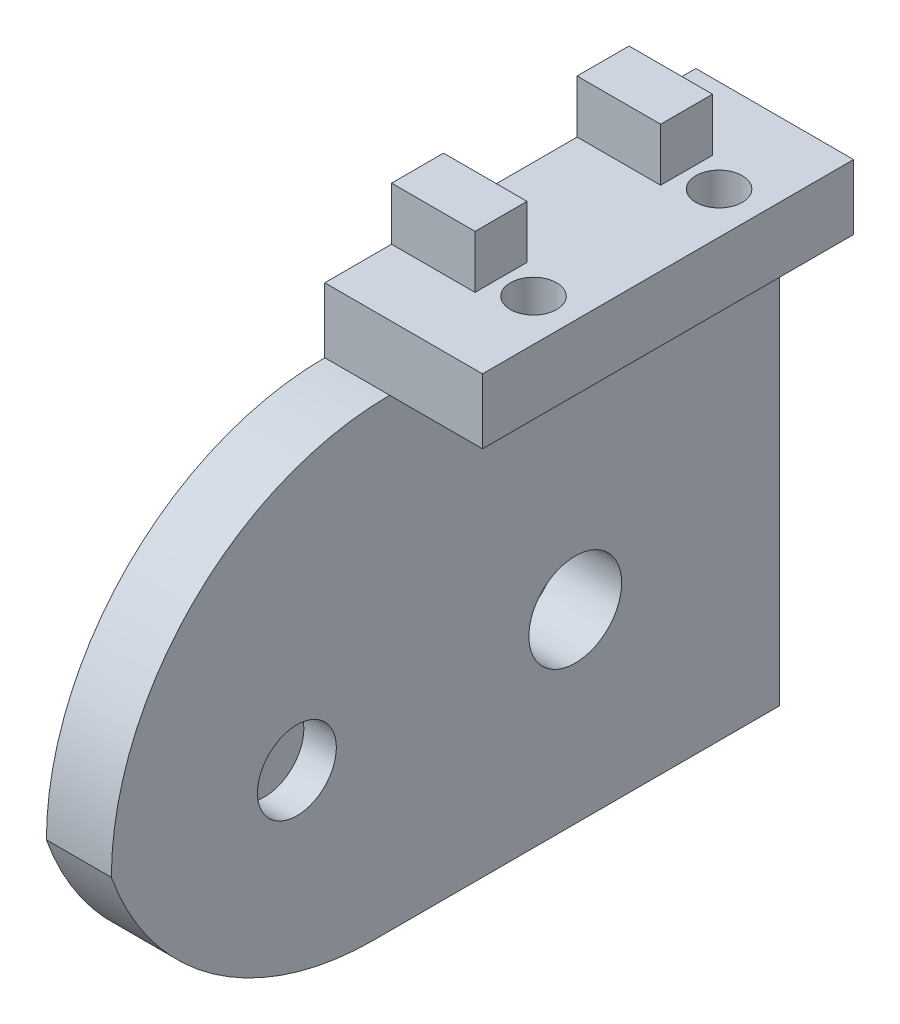
SolidWorks part; units mm, degrees
ref_plane "Alzado" through (0, 0, 0) normal (0, 0, 1) x (1, 0, 0)
ref_plane "Planta" through (0, 0, 0) normal (0, 1, 0) x (1, 0, 0)
ref_plane "Vista lateral" through (0, 0, 0) normal (1, 0, 0) x (0, 0, -1)
sketch "Croquis1" plane through (0, 0, 0) normal (0, 1, 0) x (1, 0, 0)
  line L1 (20, 20) -> (-20, 20)
  line L2 (20, 20) -> (20, -20)
  line L3 (20, -20) -> (-20, -20)
  line L4 (-20, 20) -> (-20, -20)
  line L5 (20, 20) -> (-20, -20) construction
  line L6 (20, -20) -> (-20, 20) construction
  point P0 (0, 0)
  dimension "D1" = 40
  dimension "D2" = 40
extrude "Saliente-Extruir1" add sketch "Croquis1" along normal blind 7
sketch "Croquis3" plane through (-20, 0, 0) normal (-1, 0, 0) x (0, 0, 1)
  line L0 (-20, 7) -> (20, 7) construction
  line L5 (-12.8, 12.7) -> (-7.2, 7) construction
  line L6 (7.2, 7) -> (12.8, 7)
  line L7 (7.2, 7) -> (7.2, 12.7)
  line L8 (7.2, 12.7) -> (12.8, 12.7)
  line L9 (12.8, 7) -> (12.8, 12.7)
  line L12 (-7.2, 7) -> (-12.8, 7)
  line L13 (-7.2, 7) -> (-7.2, 12.7)
  line L14 (-7.2, 12.7) -> (-12.8, 12.7)
  line L15 (-12.8, 7) -> (-12.8, 12.7)
  line L16 (-7.2, 12.7) -> (-12.8, 7) construction
  line L17 (7.2, 12.7) -> (12.8, 7) construction
  line L18 (12.8, 12.7) -> (7.2, 7) construction
  point P10 (-10, 9.85)
  point P11 (10, 9.85)
  dimension "D1" = 10
  dimension "D2" = 10
  dimension "D3" = 5.6
  dimension "D4" = 5.6
  dimension "D5" = 5.7
extrude "Saliente-Extruir3" add sketch "Croquis3" against normal up to surface (40 mm away) up to face at (20, 3.5, 0)
sketch "Croquis19" plane through (0, 12.7, 0) normal (0, 1, 0) x (1, 0, 0)
  line L0 (20, 20) -> (-20, 20) construction
  line L1 (-12, 20) -> (-20, 20)
  line L2 (-12, 20) -> (-12, -20)
  line L3 (-12, -20) -> (-20, -20)
  line L4 (-20, 20) -> (-20, -20)
  line L5 (-12, 20) -> (-20, -20) construction
  line L6 (-12, -20) -> (-20, 20) construction
  line L7 (20, 20) -> (12, 20)
  line L8 (20, 20) -> (20, -20)
  line L9 (20, -20) -> (12, -20)
  line L10 (12, 20) -> (12, -20)
  line L11 (20, 20) -> (12, -20) construction
  line L12 (20, -20) -> (12, 20) construction
  line L13 (-20, -20) -> (20, -20) construction
  line L16 (20, -7.2) -> (20, 7.2) construction
  line L17 (-20, 7.2) -> (-20, -7.2) construction
  point P0 (-16, 0)
  point P5 (16, 0)
  dimension "D1" = 8
  dimension "D4" = 8
extrude "Cortar-Extruir5" cut sketch "Croquis19" against normal up to surface (5.7 mm away) up to face at (0, 7, 0)
sketch "Croquis20" plane through (0, 7, 0) normal (0, 1, 0) x (1, 0, 0)
  line L0 (15.5, 16.9883) -> (15.5, -23.2433) construction
  line L3 (20, 20) -> (-20, 20) construction
  line L4 (-20, -20) -> (20, -20) construction
  line L5 (-15.5, 16.9883) -> (-15.5, -23.2433) construction
  line L6 (20, -20) -> (20, 20) construction
  line L7 (-20, 20) -> (-20, -20) construction
  circle A0 centre (-15.5, 10) radius 2.5
  circle A1 centre (15.5, 10) radius 2.5
  circle A2 centre (15.5, -10) radius 2.5
  circle A3 centre (-15.5, -10) radius 2.5
  dimension "D1" = 5
  dimension "D2" = 10
  dimension "D3" = 10
  dimension "D4" = 4.5
  dimension "D5" = 4.5
extrude "Cortar-Extruir6" cut sketch "Croquis20" against normal up to surface (7 mm away) up to face at (0, 0, 0)
sketch "Croquis21" plane through (0, 0, 0) normal (0, -1, 0) x (1, 0, 0)
  line L0 (-20, 20) -> (20, 20) construction
  line L10 (10, 50) -> (3, 50)
  line L11 (10, 50) -> (10, -22)
  line L12 (10, -22) -> (3, -22)
  line L13 (3, 50) -> (3, -22)
  line L14 (10, 50) -> (3, -22) construction
  line L15 (10, -22) -> (3, 50) construction
  line L18 (20, 20) -> (20, -20) construction
  point P0 (0, 0)
  point P1 (6.5, 14)
  dimension "D1" = 7
  dimension "D2" = 72
  dimension "D3" = 30
  dimension "D4" = 10
extrude "Saliente-Extruir4" add sketch "Croquis21" along normal blind 50
sketch "Croquis22" plane through (10, 0, 0) normal (1, 0, 0) x (0, 0, -1)
  line L0 (20, 0) -> (-20, 0) construction
  line L1 (22, -50) -> (-50, -50) construction
  circle A0 centre (0, -30) radius 5
  point P5 (0, 0)
  dimension "D1" = 10
  dimension "D2" = 20
extrude "Cortar-Extruir7" cut sketch "Croquis22" against normal up to surface (7 mm away) up to face at (3, -16.6667, 9.3333)
sketch "Croquis23" plane through (3, 0, 0) normal (1, 0, 0) x (0, 0, -1)
  line L1 (15.5, -14.5) -> (-15.5, -14.5) construction
  line L2 (15.5, -14.5) -> (15.5, -45.5) construction
  line L3 (15.5, -45.5) -> (-15.5, -45.5) construction
  line L4 (-15.5, -14.5) -> (-15.5, -45.5) construction
  line L5 (15.5, -14.5) -> (-15.5, -45.5) construction
  line L6 (15.5, -45.5) -> (-15.5, -14.5) construction
  point P0 (0, -30)
  dimension "D1" = 31
  dimension "D2" = 31
sketch "Croquis25" plane through (10, 0, 0) normal (1, 0, 0) x (0, 0, -1)
  circle A0 centre (-30, -30) radius 4.25
  dimension "D2" = 8.5
  dimension "D1" = 30
extrude "Cortar-Extruir8" cut sketch "Croquis25" against normal blind 3.5
fillet "Redondeo1" radius 30 1 edges at (6.5, 0, 50)
fillet "Redondeo2" radius 30 1 edges at (6.5, -50, 50)
sketch "Croquis29" plane through (-20, 0, 0) normal (-1, 0, 0) x (0, 0, 1)
  line L1 (51.8767, 89.7065) -> (-51.8767, 89.7065)
  line L2 (51.8767, 89.7065) -> (51.8767, -89.7065)
  line L3 (51.8767, -89.7065) -> (-51.8767, -89.7065)
  line L4 (-51.8767, 89.7065) -> (-51.8767, -89.7065)
  line L5 (51.8767, 89.7065) -> (-51.8767, -89.7065) construction
  line L6 (51.8767, -89.7065) -> (-51.8767, 89.7065) construction
extrude "Cortar-Extruir9" cut sketch "Croquis29" against normal up to surface (23 mm away) up to face at (3, -30, -5)
